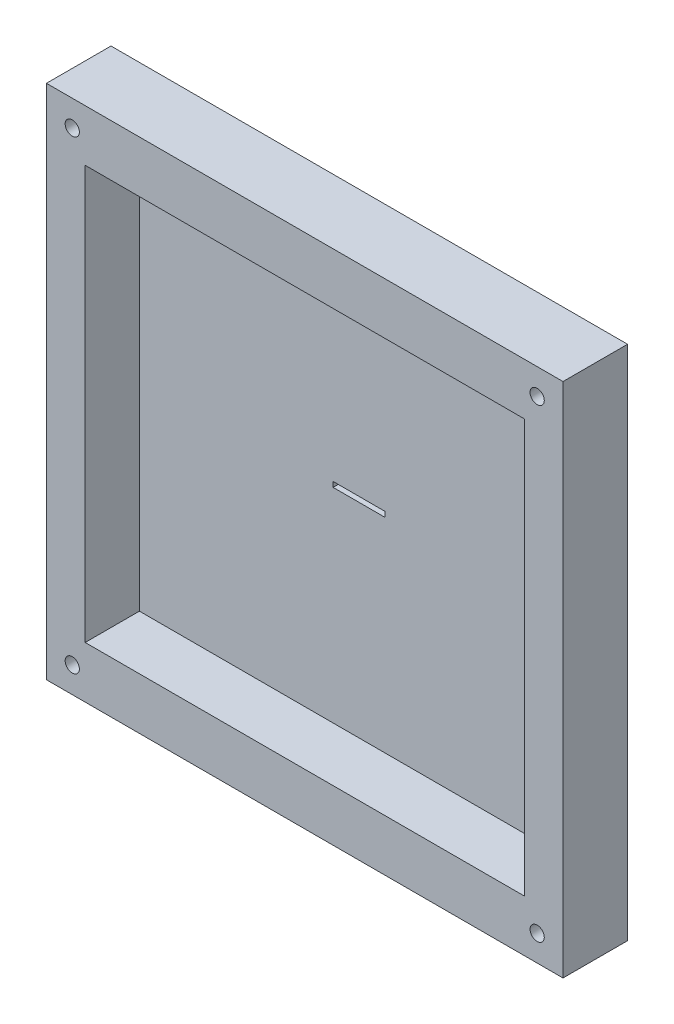
SolidWorks part; units mm, degrees
material "PA Tipo 6"
ref_plane "Plano frontal" through (0, 0, 0) normal (0, 0, 1) x (1, 0, 0)
ref_plane "Plano superior" through (0, 0, 0) normal (0, 1, 0) x (1, 0, 0)
ref_plane "Plano direito" through (0, 0, 0) normal (1, 0, 0) x (0, 0, -1)
sketch "Esboço1" plane through (0, 0, 0) normal (0, 0, 1) x (1, 0, 0)
  line L1 (-123.0692, 142.5926) -> (76.9308, 142.5926)
  line L2 (-123.0692, 142.5926) -> (-123.0692, -57.4074)
  line L3 (-123.0692, -57.4074) -> (76.9308, -57.4074)
  line L4 (76.9308, 142.5926) -> (76.9308, -57.4074)
  dimension "D1" = 200
  dimension "D2" = 200
extrude "Ressalto-extrusão1" add sketch "Esboço1" along normal blind 25
ref_plane "Plano1" through (-23.0692, 0, 0) normal (-1, 0, 0) x (0, 0, 1)
sketch "Esboço2" plane through (-23.0692, 0, 0) normal (-1, 0, 0) x (0, 0, 1)
  line L0 (25, -37.4074) -> (4, -37.4074)
  line L1 (25, -57.4074) -> (25, 35.5926) construction
  line L2 (4, -37.4074) -> (4, 122.5926)
  line L3 (4, 122.5926) -> (25, 122.5926)
  line L4 (25, 142.5926) -> (25, -57.4074) construction
  line L5 (25, 122.5926) -> (25, -37.4074)
  line L6 (25, -57.4074) -> (0, -57.4074) construction
  line L7 (25, 142.5926) -> (0, 142.5926) construction
  line L8 (0, 142.5926) -> (0, -57.4074) construction
  dimension "D1" = 20
  dimension "D2" = 20
  dimension "D3" = 4
extrude "Corte-extrusão1" cut sketch "Esboço2" against normal mid plane 170
sketch "Esboço3" plane through (0, 0, 0) normal (0, 0, -1) x (-1, 0, 0)
  line L0 (23.0692, 142.5926) -> (23.0692, -57.4074) construction
  line L1 (-76.9308, 142.5926) -> (123.0692, 142.5926) construction
  line L2 (123.0692, -57.4074) -> (-76.9308, -57.4074) construction
  line L3 (23.0692, -57.4074) -> (-76.9308, 42.5926) construction
  line L4 (-76.9308, -57.4074) -> (-76.9308, 142.5926) construction
  line L5 (-76.9308, 42.5926) -> (123.0692, 42.5926) construction
  line L6 (123.0692, 142.5926) -> (123.0692, -57.4074) construction
  circle A0 centre (-66.9308, 132.5926) radius 2.75
  circle A1 centre (113.0692, 132.5926) radius 2.75
  circle A2 centre (113.0692, -47.4074) radius 2.75
  circle A3 centre (-66.9308, -47.4074) radius 2.75
  dimension "D1" = 5.5
  dimension "D2" = 10
  dimension "D3" = 10
extrude "Corte-extrusão2" cut sketch "Esboço3" against normal blind 30
sketch "Esboço4" plane through (0, 0, 0) normal (0, 0, -1) x (-1, 0, 0)
  line L0 (-76.9308, 42.5926) -> (123.0692, 42.5926) construction
  line L1 (-76.9308, -57.4074) -> (-76.9308, 142.5926) construction
  line L2 (123.0692, 142.5926) -> (123.0692, -57.4074) construction
  line L3 (123.0692, 42.5926) -> (23.0692, -57.4074) construction
  line L4 (123.0692, -57.4074) -> (-76.9308, -57.4074) construction
  line L5 (23.0692, -57.4074) -> (23.0692, 142.5926) construction
  line L6 (23.0692, -13.75) -> (23.0692, 13.75) construction
  line L8 (13.0692, 41.5926) -> (33.0692, 41.5926)
  line L9 (13.0692, 41.5926) -> (13.0692, 43.5926)
  line L10 (13.0692, 43.5926) -> (33.0692, 43.5926)
  line L11 (33.0692, 41.5926) -> (33.0692, 43.5926)
  line L12 (13.0692, 41.5926) -> (33.0692, 43.5926) construction
  line L13 (13.0692, 43.5926) -> (33.0692, 41.5926) construction
  point P6 (23.0692, 42.5926)
  dimension "D1" = 20
  dimension "D2" = 2
extrude "Corte-extrusão3" cut sketch "Esboço4" against normal through all both and the other way through all
sketch "Esboço5" plane through (0, 0, 0) normal (0, 0, -1) x (-1, 0, 0)
  line L0 (-48.9444, 132.5926) -> (-48.9444, -47.4074) construction
  text T0 "Aluno: Mardden Mangabeira Maia\r\nProf. Dr. Vergílio Torezan Silingardi Del Claro" font "Century Gothic" height 5
extrude "Corte-extrusão4" cut sketch "Esboço5" against normal blind 2
